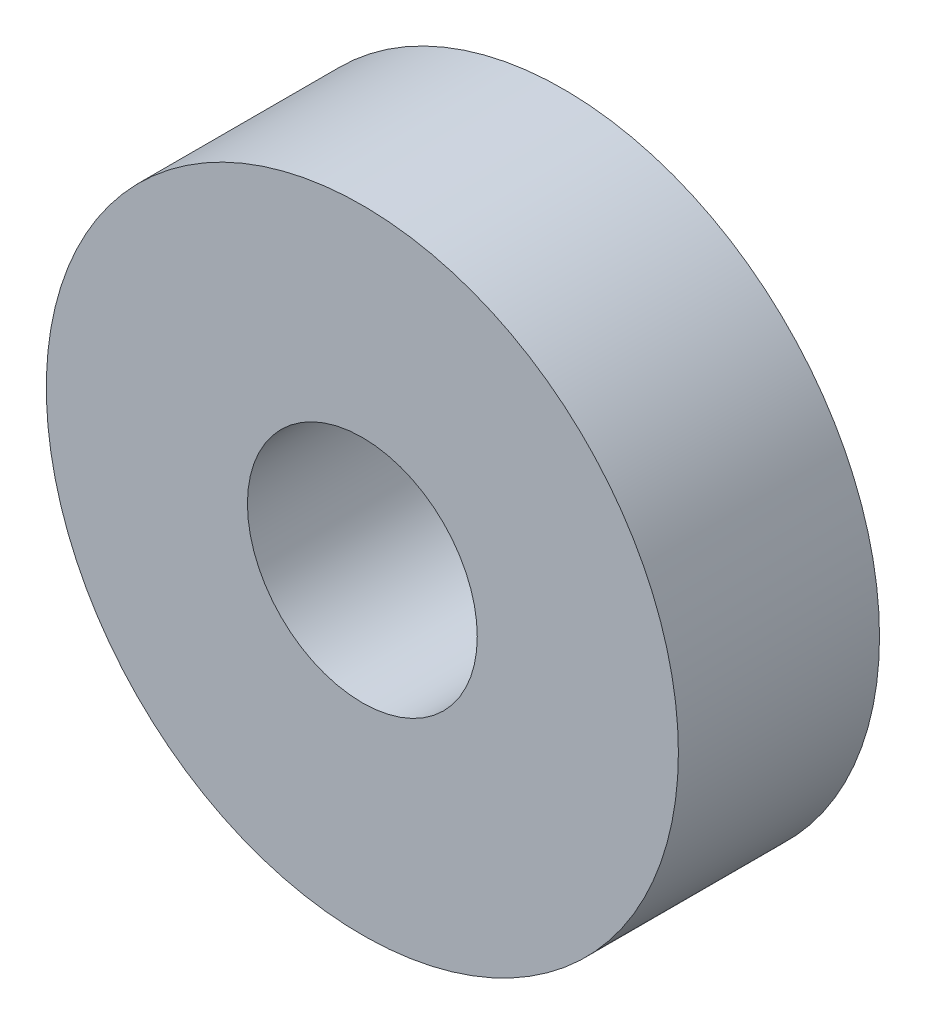
SolidWorks part; units mm, degrees
ref_plane "Front Plane" through (0, 0, 0) normal (0, 0, 1) x (1, 0, 0)
ref_plane "Top Plane" through (0, 0, 0) normal (0, 1, 0) x (1, 0, 0)
ref_plane "Right Plane" through (0, 0, 0) normal (1, 0, 0) x (0, 0, -1)
ref_plane "Plane1" through (0, 0, 7) normal (0, 0, 1) x (1, 0, 0)
sketch "Sketch1" plane through (0, 0, 7) normal (0, 0, 1) x (1, 0, 0)
  circle A0 centre (0, 0) radius 11
extrude "Boss-Extrude1" add sketch "Sketch1" against normal blind 7
hole_wizard "Ø8.0 (8) Diameter Hole1" positions "Sketch3" profile "Sketch2" hole size "Ø8.0" standard "ANSI Metric"
sketch "Sketch3" plane through (0, 0, 7) normal (0, 0, 1) x (1, 0, 0)
  point P0 (0, 0)
sketch "Sketch2" plane through (0, 0, 7) normal (1, 0, 0) x (0, -1, 0)
  line L0 (0, 0) -> (0, 7)
  line L1 (0, 7) -> (4, 7)
  line L2 (4, 7) -> (4, 0)
  line L5 (4, 0) -> (0, 0)
  line L11 (0, -6.35) -> (0, 107.95) construction
  dimension "Thru Hole Dia." = 8
  dimension "Thru Hole Depth" = 7
ref_axis "Axis1" through (0, 0, -4.0155) along (0, 0, 1)
